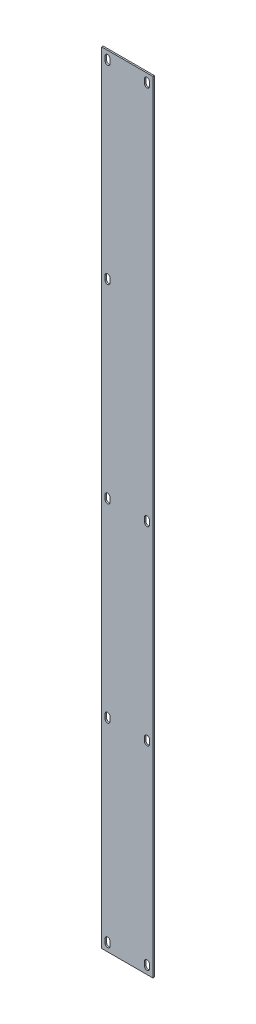
SolidWorks part; units mm, degrees
ref_plane "Front Plane" through (0, 0, 0) normal (0, 0, 1) x (1, 0, 0)
ref_plane "Top Plane" through (0, 0, 0) normal (0, 1, 0) x (1, 0, 0)
ref_plane "Right Plane" through (0, 0, 0) normal (1, 0, 0) x (0, 0, -1)
sketch "Sketch1" plane through (0, 0, 0) normal (0, 1, 0) x (1, 0, 0)
  line L1 (-13.85, -0.4064) -> (13.85, -0.4064)
  line L2 (-13.85, -0.4064) -> (-13.85, 0.4064)
  line L3 (-13.85, 0.4064) -> (13.85, 0.4064)
  line L4 (13.85, -0.4064) -> (13.85, 0.4064)
  line L5 (-13.85, -0.4064) -> (13.85, 0.4064) construction
  line L6 (-13.85, 0.4064) -> (13.85, -0.4064) construction
  point P0 (0, 0)
  dimension "D1" = 27.7
  dimension "D2" = 0.8128
extrude "Boss-Extrude1" add sketch "Sketch1" along normal blind 422.91
hole_wizard "M2.5 Clearance Slot2" positions "Sketch8" profile "Sketch9" size "M2.5" standard "ANSI Metric" slot yes end condition up to next
sketch "Sketch8" plane through (0, 0, -0.4064) normal (0, 0, -1) x (-1, 0, 0)
  line L1 (10.675, 0) -> (10.675, 422.91) construction
  line L3 (13.85, 422.91) -> (13.85, 0) construction
  line L4 (-10.675, 2) -> (-10.675, 7) construction
  line L5 (-13.85, 0) -> (13.85, 0) construction
  line L14 (-13.85, 0) -> (13.85, 0)
  line L15 (13.85, 0) -> (13.85, 422.91)
  line L16 (13.85, 422.91) -> (-13.85, 422.91)
  line L17 (-13.85, 422.91) -> (-13.85, 0)
  line L18 (-13.85, 0) -> (13.85, 0) construction
  line L19 (13.85, 0) -> (13.85, 422.91) construction
  line L20 (13.85, 422.91) -> (-13.85, 422.91) construction
  line L21 (-13.85, 422.91) -> (-13.85, 0) construction
  line L22 (-10.675, 418.41) -> (-10.675, 315.5575) construction
  line L23 (-10.675, 212.705) -> (-10.675, 109.8525) construction
  line L24 (-10.675, 109.8525) -> (-10.675, 7) construction
  line L25 (-10.675, 315.5575) -> (-10.675, 212.705) construction
  point P11 (-10.675, 4.5)
  point P23 (10.675, 4.5)
  point P28 (-10.675, 418.41)
  point P30 (10.675, 418.41)
  point P63 (-10.675, 212.705)
  point P64 (10.675, 315.5575)
  point P68 (-10.675, 109.8525)
  point P69 (10.675, 212.705)
  point P76 (10.675, 109.8525)
  point P81 (0, 0)
  point P82 (0, 0)
  dimension "D1" = 3.175
  dimension "D2" = 3.175
  dimension "D3" = 5
  dimension "D4" = 4.5
  dimension "D5" = 4.5
  dimension "D6" = 0
sketch "Sketch9" plane through (-10.675, 109.8525, -0.4064) normal (1, 0, 0) x (0, 1, 0)
  line L0 (0, 0) -> (0, 0.8128)
  line L1 (0, 0.8128) -> (1.35, 0.8128)
  line L2 (1.35, 0.8128) -> (1.35, 0)
  line L5 (1.35, 0) -> (0, 0)
  line L11 (0, -6.35) -> (0, 107.95) construction
  dimension "Thru Hole Dia." = 2.7
  dimension "Thru Hole Depth" = 0.8128
